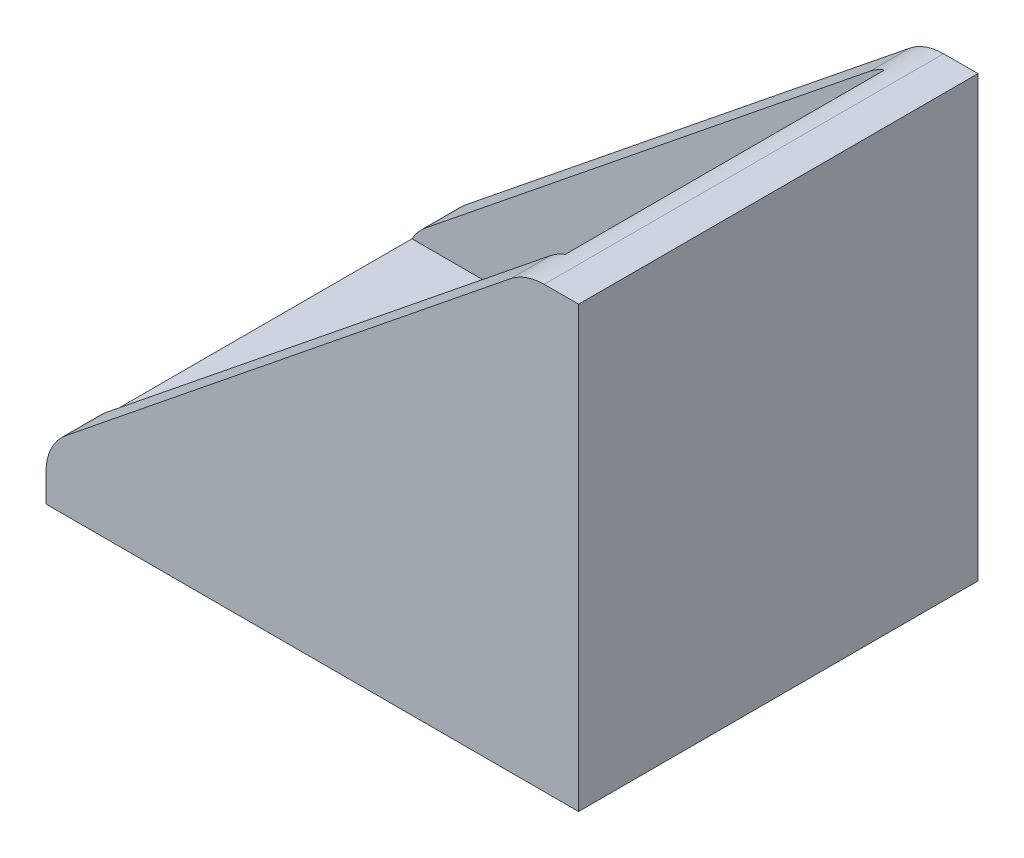
SolidWorks part; units mm, degrees
material "ABS"
ref_plane "Front Plane" through (0, 0, 0) normal (0, 0, 1) x (1, 0, 0)
ref_plane "Top Plane" through (0, 0, 0) normal (0, 1, 0) x (1, 0, 0)
ref_plane "Right Plane" through (0, 0, 0) normal (1, 0, 0) x (0, 0, -1)
sketch "Sketch1" plane through (0, 0, 0) normal (0, 0, 1) x (1, 0, 0)
  line L0 (-50.8, 0) -> (0, 0)
  line L1 (0, 0) -> (0, 41.91)
  line L2 (-50.8, 5.08) -> (-5.08, 5.08)
  line L3 (-5.08, 5.08) -> (-5.08, 41.91)
  line L4 (-50.8, 0) -> (-50.8, 5.08)
  line L5 (0, 41.91) -> (-5.08, 41.91)
  dimension "D2" = 41.91
  dimension "D3" = 5.08
extrude "Boss-Extrude1" add sketch "Sketch1" along normal blind 38.1
ref_plane "midplane" through (0, 0, 19.05) normal (0, 0, 1) x (1, 0, 0)
sketch "Sketch6" plane through (0, 0, 0) normal (0, 0, 1) x (1, 0, 0)
  line L0 (-50.8, 5.08) -> (-5.08, 5.08)
  line L2 (-5.08, 5.08) -> (-5.08, 41.91)
  line L4 (-50.8, 5.08) -> (-5.08, 41.91)
extrude "Boss-Extrude2" add sketch "Sketch6" along normal blind 3.81 contours L2 L4 L0
mirror "Mirror1" about plane through (0, 0, 19.05) normal (0, 0, 1) of "Boss-Extrude2"
fillet "Fillet3" radius 5.08 2 edges at (-5.08, 41.91, 1.905) (-50.8, 5.08, 1.905) tangent propagation no
sketch "Sketch2" plane through (0, 5.08, 0) normal (0, 1, 0) x (1, 0, 0)
  line L0 (-50.1806, -19.05) -> (-5.08, -19.05) construction
  line L3 (-50.1806, -3.81) -> (-50.1806, -34.29) construction
  line L6 (-40.3303, -19.05) -> (-14.9303, -19.05) construction
  line L7 (-40.3303, -15.875) -> (-14.9303, -15.875)
  line L8 (-40.3303, -22.225) -> (-14.9303, -22.225)
  line L9 (-5.08, -34.29) -> (-5.08, -3.81) construction
  arc A0 (-40.3303, -15.875) -> (-40.3303, -22.225) centre (-40.3303, -19.05) ccw
  arc A1 (-14.9303, -22.225) -> (-14.9303, -15.875) centre (-14.9303, -19.05) ccw
  point P11 (-27.6303, -19.05)
  point P14 (-27.6303, -19.05)
  dimension "D2" = 25.4
  dimension "D1" = 6.35
extrude "Cut-Extrude1" cut sketch "Sketch2" against normal up to next
sketch "Sketch8" plane through (0, 0, 38.1) normal (0, 0, 1) x (1, 0, 0)
  line L0 (0, 0) -> (0.7315, 41.91)
  line L1 (0.7315, 41.91) -> (0, 41.91)
  line L2 (0, 41.91) -> (0, 0)
  dimension "D1" = 1
equation "\"horizDist\"= 2"
equation "\"vertDist\"= 1.65"
equation "\"D1@Sketch1\"=\"horizDist\""
equation "\"D2@Sketch1\"=\"vertDist\""
equation "\"t\"= .2"
equation "\"D3@Sketch1\"=\"t\""
equation "\"horizWidth\"= 1.5"
equation "\"D1@Boss-Extrude1\"=\"horizWidth\""
equation "\"D1@Boss-Extrude2\"=\"horizWidth\"/10"
